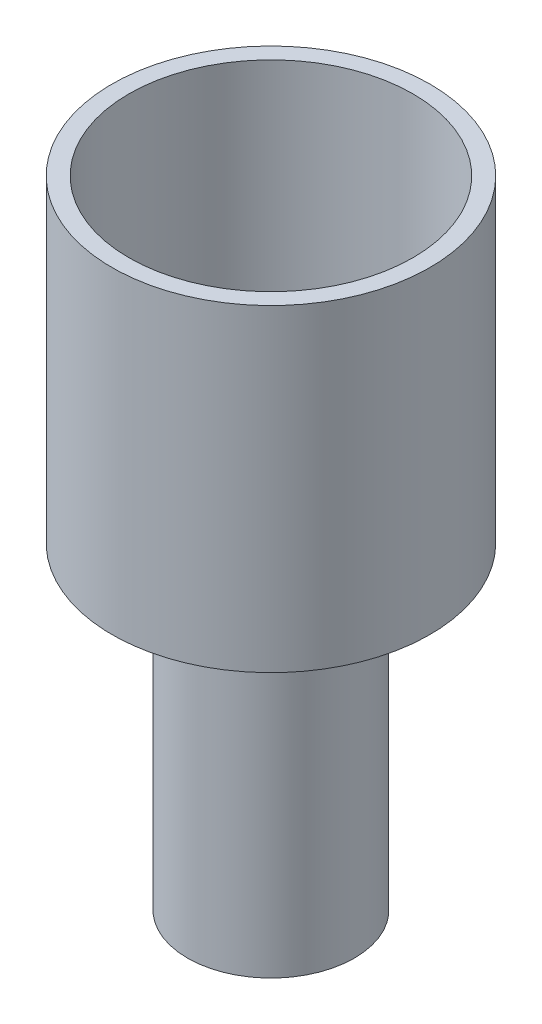
SolidWorks part; units mm, degrees
note: The reader was unsure of these and kept them because the rebuilt part matched: shared geometry of "Sketch2<3>".
material "6061-T4 (SS)"
ref_plane "Front Plane" through (0, 0, 0) normal (0, 0, 1) x (1, 0, 0)
ref_plane "Top Plane" through (0, 0, 0) normal (0, 1, 0) x (1, 0, 0)
ref_plane "Right Plane" through (0, 0, 0) normal (1, 0, 0) x (0, 0, -1)
sketch "Sketch1" plane through (0, 0, 0) normal (0, 0, 1) x (1, 0, 0)
  line L0 (-9.525, 19.05) -> (-9.525, 0)
  line L1 (-9.525, 0) -> (-5, 0)
  line L2 (-5, 0) -> (-5, -19.05)
  line L3 (0, -15.8578) -> (0, 15.6451) construction
  dimension "D1" = 10
  dimension "D2" = 19.05
  dimension "D3" = 19.05
  dimension "D4" = 19.05
sketch "Sketch2" plane through (0, 0, 0) normal (0, 1, 0) x (1, 0, 0)
  circle A0 centre (0, 0) radius 9.525
  circle A1 centre (0, 0) radius 5
extrude "Boss-Extrude1" add sketch "Sketch2" along normal up to vertex (19.05 mm away) contours A0 A1 | A1 up to point (-9.525, 19.05, 0)
extrude "Boss-Extrude2" add sketch "Sketch2<3>" against normal up to vertex (19.05 mm away) contours A1 up to point (-5, -19.05, 0)
sketch "Sketch2<3>" plane through (0, 0, 0) normal (0, 1, 0) x (1, 0, 0) same geometry as "Sketch2"
hole_wizard "5/8 (0.625) Diameter Hole1" [suppressed] positions "Sketch7" profile "Sketch6" hole size "5/8" standard "ANSI Inch"
sketch "Sketch7" plane through (0, 19.05, 0) normal (0, 1, 0) x (1, 0, 0)
  point P0 (0, 0)
sketch "Sketch6" plane through (0, 19.05, 0) normal (1, 0, 0) x (0, 0, 1)
  line L0 (0, 0) -> (0, 25.4)
  line L1 (0, 25.4) -> (7.9375, 20.6307)
  line L2 (7.9375, 20.6307) -> (7.9375, 0)
  line L5 (7.9375, 0) -> (0, 0)
  line L10 (0, 25.4) -> (-7.9375, 20.6307) construction
  line L11 (0, -6.35) -> (0, 107.95) construction
  dimension "Hole Dia." = 15.875
  dimension "Hole Depth" = 25.4
  dimension "Drill Angle" = 118
hole_wizard "11/32 (0.34375) Diameter Hole1" positions "Sketch12" profile "Sketch11" hole size "11/32" standard "ANSI Inch" end condition through all
sketch "Sketch12" plane through (0, -19.05, 0) normal (0, -1, 0) x (-1, 0, 0)
  point P0 (0, 0)
sketch "Sketch11" plane through (0, -19.05, 0) normal (1, 0, 0) x (0, 0, -1)
  line L0 (0, 0) -> (0, 38.1)
  line L1 (0, 38.1) -> (4.3656, 38.1)
  line L2 (4.3656, 38.1) -> (4.3656, 0)
  line L5 (4.3656, 0) -> (0, 0)
  line L11 (0, -6.35) -> (0, 107.95) construction
  dimension "Thru Hole Dia." = 8.7312
  dimension "Thru Hole Depth" = 38.1
sketch "Sketch13" plane through (0, 19.05, 0) normal (0, 1, 0) x (1, 0, 0)
  circle A2 centre (0, 0) radius 8.509
  circle A3 centre (0, 0) radius 8.509
  dimension "D1" = 1.016
extrude "Cut-Extrude1" cut sketch "Sketch13" against normal blind 17.78
ref_plane "Plane1" through (0, 15.24, 0) normal (0, 1, 0) x (1, 0, 0)
